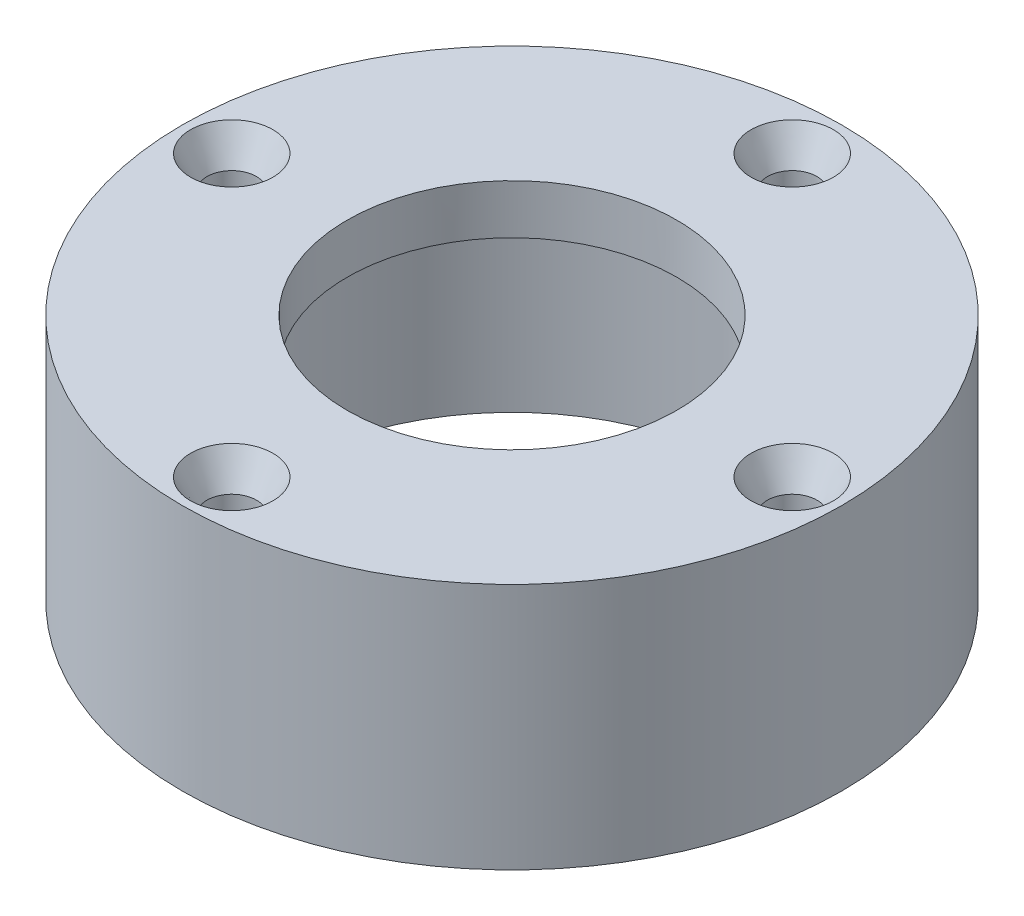
SolidWorks part; units mm, degrees
ref_plane "Front Plane" through (0, 0, 0) normal (0, 0, 1) x (1, 0, 0)
ref_plane "Top Plane" through (0, 0, 0) normal (0, 1, 0) x (1, 0, 0)
ref_plane "Right Plane" through (0, 0, 0) normal (1, 0, 0) x (0, 0, -1)
sketch "Sketch1" plane through (0, 0, 0) normal (0, 1, 0) x (1, 0, 0)
  circle A0 centre (0, 0) radius 20
extrude "Boss-Extrude1" add sketch "Sketch1" along normal blind 15
sketch "Sketch4" plane through (0, 0, 0) normal (0, -1, 0) x (1, 0, 0)
  circle A0 centre (0, 0) radius 14
extrude "Cut-Extrude3" cut sketch "Sketch4" against normal blind 12
sketch "Sketch5" plane through (0, 15, 0) normal (0, 1, 0) x (1, 0, 0)
  circle A0 centre (0, 0) radius 10
extrude "Cut-Extrude4" cut sketch "Sketch5" against normal blind 12
sketch "Sketch6" plane through (0, 15, 0) normal (0, 1, 0) x (1, 0, 0)
  line L0 (0, 0) -> (0, 28.6341) construction
  line L1 (0, 0) -> (42.7374, 0) construction
  circle A0 centre (0, 17) radius 1.5
  circle A1 centre (17, 0) radius 1.5
  circle A2 centre (0, -17) radius 1.5
  circle A3 centre (-17, 0) radius 1.5
  point P18 (0, 0)
  dimension "D1" = 17
extrude "Cut-Extrude5" cut sketch "Sketch6" against normal through all
sketch "Sketch7" plane through (0, 15, 0) normal (0, 1, 0) x (1, 0, 0)
  circle A0 centre (0, 17) radius 2.5
  circle A1 centre (17, 0) radius 2.5
  circle A2 centre (0, -17) radius 2.5
  circle A3 centre (-17, 0) radius 2.5
  point P12 (0, 0)
  dimension "D1" = 4
extrude "Cut-Extrude7" cut sketch "Sketch7" against normal blind 2 draft 27
